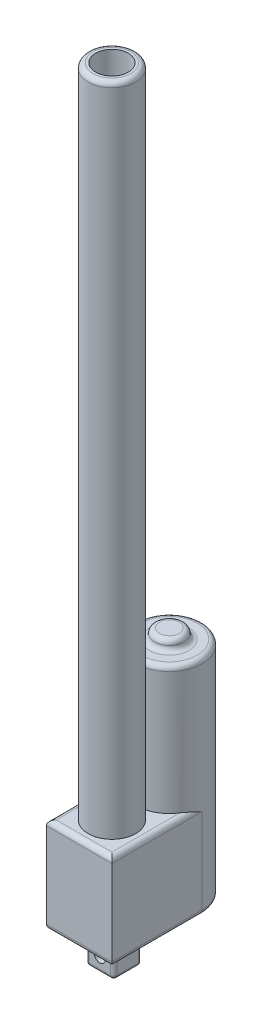
SolidWorks part; units mm, degrees
ref_plane "前视基准面" through (0, 0, 0) normal (0, 0, 1) x (1, 0, 0)
ref_plane "上视基准面" through (0, 0, 0) normal (0, 1, 0) x (1, 0, 0)
ref_plane "右视基准面" through (0, 0, 0) normal (1, 0, 0) x (0, 0, -1)
other "Configuration Table"
sketch "草图1" plane through (0, 0, 0) normal (0, 1, 0) x (1, 0, 0)
  line L0 (0, 0) -> (0, -42.7412) construction
  line L1 (20, 0) -> (20, -55)
  line L2 (-20, 0) -> (-20, -55)
  line L3 (0, -55) -> (63.3032, -55) construction
  line L4 (-20, -55) -> (20, -55)
  arc A0 (20, 0) -> (-20, 0) centre (0, 0) ccw
  point P3 (0, -42.7412)
  dimension "D2" = 20
  dimension "D3" = 20
  dimension "D1" = 40
  dimension "D4" = 55
extrude "凸台-拉伸1" add sketch "草图1" along normal blind 58
sketch "草图2" plane through (0, 58, 0) normal (0, 1, 0) x (1, 0, 0)
  circle A2 centre (0, 0) radius 20
  dimension "D3" = 40
extrude "凸台-拉伸7" add sketch "草图2" along normal blind 78 contours A2
sketch "草图3" plane through (0, 58, 0) normal (0, 1, 0) x (1, 0, 0)
  line L0 (20, -55) -> (20, 0) construction
  line L1 (-20, -55) -> (20, -55) construction
  circle A0 centre (0, -35) radius 14.5
  dimension "D1" = 29
  dimension "D3" = 20
  dimension "D2" = 20
extrude "凸台-拉伸8" add sketch "草图3" along normal blind 400
sketch "草图4" plane through (0, 458, 0) normal (0, 1, 0) x (1, 0, 0)
  circle A2 centre (0, -35) radius 10
  dimension "D1" = 20
extrude "切除-拉伸1" cut sketch "草图4" against normal blind 300
fillet "圆角2" radius 3 3 edges at (0, 58, 55) (20, 58, 27.5) (-20, 58, 27.5)
fillet "圆角3" radius 3 4 edges at (0, 0, -20) (20, 0, 27.5) (0, 0, 55) (-20, 0, 27.5)
fillet "圆角4" radius 3 1 edges at (0, 136, 20)
sketch "草图6" plane through (0, 136, 0) normal (0, 1, 0) x (1, 0, 0)
  circle A0 centre (0, 0) radius 9
  dimension "D1" = 18
extrude "凸台-拉伸10" add sketch "草图6" along normal blind 6
fillet "圆角5" radius 3 2 edges at (0, 142, 9) (0, 136, 9)
fillet "圆角6" radius 3 1 edges at (0, 458, 49.5)
sketch "草图7" plane through (0, 0, 0) normal (0, -1, 0) x (1, 0, 0)
  line L1 (-5.4046, 43.5) -> (7.5954, 43.5)
  line L2 (-7.4046, 41.5) -> (-7.4046, 28.5)
  line L9 (-5.4046, 26.5) -> (7.5954, 26.5)
  line L10 (9.5954, 41.5) -> (9.5954, 28.5)
  line L11 (1.0954, 26.5) -> (1.0954, 43.5) construction
  line L12 (-7.4046, 35) -> (9.5954, 35) construction
  arc A0 (-7.4046, 41.5) -> (-5.4046, 43.5) centre (-5.4046, 41.5) cw
  arc A3 (-5.4046, 26.5) -> (-7.4046, 28.5) centre (-5.4046, 28.5) cw
  arc A4 (9.5954, 28.5) -> (7.5954, 26.5) centre (7.5954, 28.5) cw
  arc A5 (9.5954, 41.5) -> (7.5954, 43.5) centre (7.5954, 41.5) ccw
  point P14 (9.5954, 26.5)
  point P17 (9.5954, 43.5)
  dimension "D3" = 2
  dimension "D4" = 2
  dimension "D2" = 17
  dimension "D5" = 17
extrude "凸台-拉伸11" add sketch "草图7" along normal blind 18
sketch "草图8" plane through (9.5954, 0, 0) normal (1, 0, 0) x (0, 0, -1)
  line L0 (-35, -18) -> (-35, -2.0044) construction
  line L1 (-28.5, -18) -> (-41.5, -18) construction
  line L3 (-28.5, 0) -> (-41.5, 0) construction
  circle A0 centre (-35, -9.5) radius 3.25
  dimension "D1" = 6.5
  dimension "D2" = 9.5
fillet "圆角7" radius 2 8 edges at (-7.4046, -18, 35) (-6.8188, -18, 42.9142) (-6.8188, -18, 27.0858) (1.0954, -18, 26.5) (9.0097, -18, 27.0858) (1.0954, -18, 43.5) (9.0097, -18, 42.9142) (9.5954, -18, 35)
sketch "草图9" plane through (0, 0, 43.5) normal (0, 0, 1) x (1, 0, 0)
  line L0 (1.0954, -17.2237) -> (1.0954, 3.9948) construction
  line L2 (7.5954, 0) -> (-5.4046, 0) construction
  circle A0 centre (1.0954, -9.5) radius 3.25
  dimension "D1" = 6.5
  dimension "D2" = 9.5
extrude "切除-拉伸2" cut sketch "草图9" against normal through all
